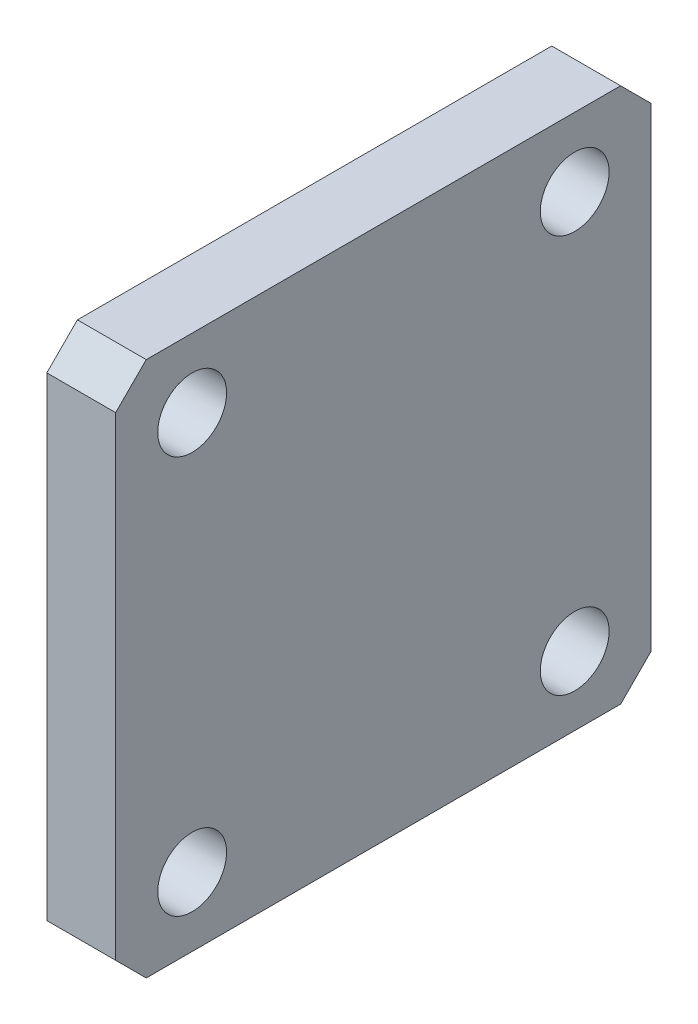
SolidWorks part; units mm, degrees
ref_plane "Спереди" through (0, 0, 0) normal (0, 0, 1) x (1, 0, 0)
ref_plane "Сверху" through (0, 0, 0) normal (0, 1, 0) x (1, 0, 0)
ref_plane "Справа" through (0, 0, 0) normal (1, 0, 0) x (0, 0, -1)
sketch "Эскиз1" plane through (0, 0, 0) normal (1, 0, 0) x (0, 0, -1)
  line L1 (-17.5, -17.5) -> (17.5, -17.5)
  line L2 (-17.5, -17.5) -> (-17.5, 17.5)
  line L3 (-17.5, 17.5) -> (17.5, 17.5)
  line L4 (17.5, -17.5) -> (17.5, 17.5)
  line L5 (-17.5, -17.5) -> (17.5, 17.5) construction
  line L6 (-17.5, 17.5) -> (17.5, -17.5) construction
  point P0 (0, 0)
  dimension "D1" = 35
  dimension "D2" = 35
extrude "Бобышка-Вытянуть1" add sketch "Эскиз1" along normal blind 4.5
chamfer "Фаска1" distance 2 angle 45 4 edges at (2.25, -17.5, -17.5) (2.25, 17.5, -17.5) (2.25, -17.5, 17.5) (2.25, 17.5, 17.5)
sketch "Эскиз2" plane through (4.5, 0, 0) normal (1, 0, 0) x (0, 0, -1)
  point P0 (12.5, 13)
  dimension "D1" = 13
  dimension "D2" = 12.5
hole_wizard "Отверстие с зазором M41" positions "Трехмерный эскиз1" profile "Эскиз3" hole size "M4" standard "ISO"
sketch3d "Трехмерный эскиз1"
  point P0 (4.5, 13, -12.5)
sketch "Эскиз3" plane through (4.5, 13, -12.5) normal (0, 1, 0) x (0, 0, -1)
  line L0 (0, 0) -> (0, 21.3519)
  line L1 (0, 21.3519) -> (2.25, 20)
  line L2 (2.25, 20) -> (2.25, 0)
  line L5 (2.25, 0) -> (0, 0)
  line L10 (0, 21.3519) -> (-2.25, 20) construction
  line L11 (0, -6.35) -> (0, 107.95) construction
  dimension "Диаметр отверстия" = 4.5
  dimension "Глубина отверстия" = 20
  dimension "Угол заточки сверла" = 118
ref_axis "Ось1" through (-17.3885, 0, 0) along (1, 0, 0)
pattern_linear "Линейный массив1" count 2 spacing 25 along (0, 0, 1) count 2 spacing 26 along (0, -1, 0) of "Отверстие с зазором M41"
